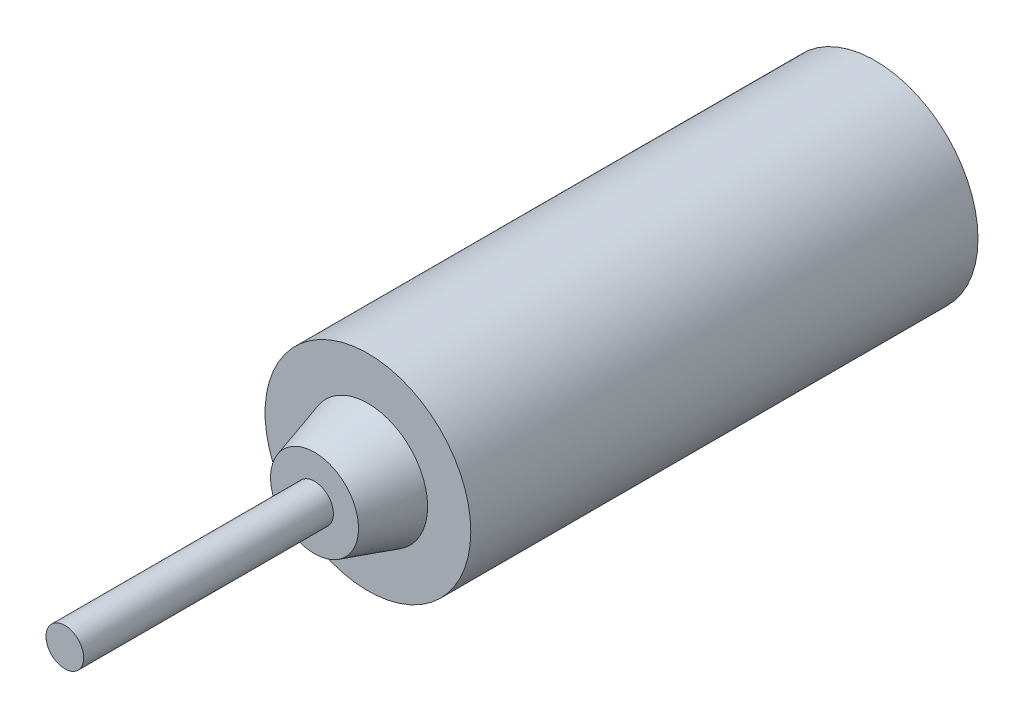
SolidWorks part; units mm, degrees
ref_plane "Front Plane" through (0, 0, 0) normal (0, 0, 1) x (1, 0, 0)
ref_plane "Top Plane" through (0, 0, 0) normal (0, 1, 0) x (1, 0, 0)
ref_plane "Right Plane" through (0, 0, 0) normal (1, 0, 0) x (0, 0, -1)
sketch "Sketch1" plane through (0, 0, 0) normal (0, 0, 1) x (1, 0, 0)
  circle A0 centre (0, 0) radius 32.75
  dimension "D1" = 65.5
extrude "Boss-Extrude1" add sketch "Sketch1" against normal mid plane 161.5
sketch "Sketch10" plane through (0, 0, 0) normal (1, 0, 0) x (0, 0, -1)
  line L0 (-97.75, 0) -> (-97.75, 14)
  line L1 (-80.75, 19) -> (-97.75, 14)
  line L2 (-1000, 0) -> (49000, 0) construction
  line L3 (-97.75, 0) -> (-80.75, 0)
  line L4 (-80.75, 0) -> (-80.75, 19)
  line L6 (-80.75, 32.75) -> (-80.75, -32.75) construction
  point P2 (-80.75, 20.8205)
  point P3 (-97.75, 0)
  dimension "D1" = 14
  dimension "D2" = 17
  dimension "D3" = 19
revolve "Revolve1" add sketch "Sketch10" angle 360 about L2
sketch "Sketch12" plane through (0, 0, 97.75) normal (0, 0, 1) x (1, 0, 0)
  circle A0 centre (0, 0) radius 6
  dimension "D1" = 12
extrude "Boss-Extrude5" add sketch "Sketch12" along normal blind 79.5
